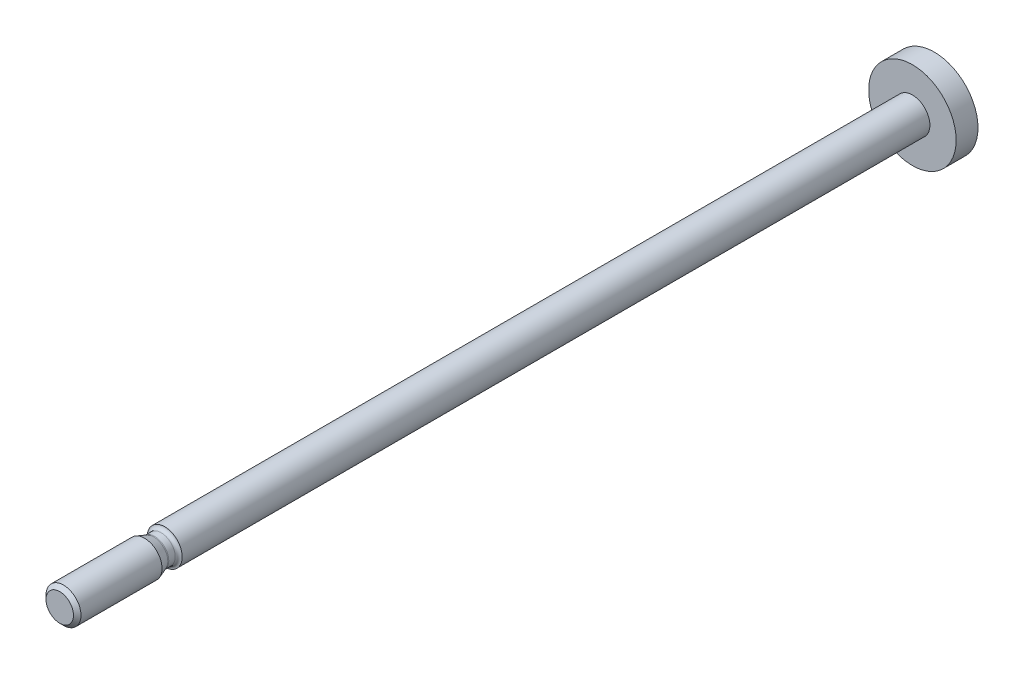
SolidWorks part; units mm, degrees
ref_plane "Front Plane" through (0, 0, 0) normal (0, 0, 1) x (1, 0, 0)
ref_plane "Top Plane" through (0, 0, 0) normal (0, 1, 0) x (1, 0, 0)
ref_plane "Right Plane" through (0, 0, 0) normal (1, 0, 0) x (0, 0, -1)
sketch "Sketch1" plane through (0, 0, 0) normal (1, 0, 0) x (0, 0, -1)
  line L0 (-4, 0) -> (-4, 2)
  line L1 (-4, 2) -> (81.5, 2)
  line L2 (81.5, 2) -> (81.5, 5)
  line L3 (81.5, 5) -> (84, 5)
  line L4 (84, 5) -> (84, 0)
  line L5 (84, 0) -> (-4, 0)
  line L6 (84, 0) -> (-4, 0) construction
revolve "Revolve1" add sketch "Sketch1" angle 360 about L6 reverse direction yes
sketch "Sketch2" plane through (0, 0, 0) normal (1, 0, 0) x (0, 0, -1)
  line L0 (-16, 0) -> (-16, 1.5705)
  line L1 (-16, 1.5705) -> (-15.5705, 2)
  line L2 (-15.5705, 2) -> (-6.299, 2)
  line L3 (-6.299, 2) -> (-5.2663, 1.6241)
  line L4 (-5.1295, 1.6) -> (-4.4, 1.6)
  line L5 (-4, 2) -> (-3, 2)
  line L6 (-3, 2) -> (-3, 0)
  line L7 (-3, 0) -> (-16, 0)
  line L8 (-3, 0) -> (-16, 0) construction
  arc A0 (-5.2663, 1.6241) -> (-5.1295, 1.6) centre (-5.1295, 2) ccw
  arc A1 (-4.4, 1.6) -> (-4, 2) centre (-4.4, 2) ccw
revolve "Revolve2" add sketch "Sketch2" angle 360 about L8 reverse direction yes
cosmetic thread "Cosmetic Thread1" parameters "D1"=9.701, "D2"=3.141
ref_plane "Plane1" through (0, 0, 4) normal (0, 0, 1) x (1, 0, 0)
ref_plane "Plane2" through (0, 0, -174) normal (0, 0, 1) x (1, 0, 0)
ref_plane "Plane3" through (0, 0, 12) normal (0, 0, 1) x (1, 0, 0)
ref_plane "Plane4" through (0, 0, 8.2) normal (0, 0, 1) x (1, 0, 0)
ref_plane "FDT_KSAUFSATZ XY" through (0, 0, 8.2) normal (0, 0, 1) x (1, 0, 0)
ref_plane "FDT_KSAUFSATZ XZ" through (0, 0, 0) normal (0, 1, 0) x (1, 0, 0)
ref_plane "FDT_KSAUFSATZ YZ" through (0, 0, 0) normal (-1, 0, 0) x (0, 0, 1)
ref_axis "FDT_KSAUFSATZ X" through (80.9, 0, 8.2) along (-1, 0, 0)
ref_axis "FDT_KSAUFSATZ Y" through (0, 50, 8.2) along (0, -1, 0)
ref_axis "FDT_KSAUFSATZ Z" through (0, 0, 80.9) along (0, 0, -1)
sketch3d "FDT_KSAUFSATZ"
  point P0 (0, 0, 8.2)
ref_plane "FDT_NUT XY" through (0, 0, 8.2) normal (0, 0, 1) x (1, 0, 0)
ref_plane "FDT_NUT XZ" through (0, 0, 0) normal (0, 1, 0) x (1, 0, 0)
ref_plane "FDT_NUT YZ" through (0, 0, 0) normal (-1, 0, 0) x (0, 0, 1)
ref_axis "FDT_NUT X" through (80.9, 0, 8.2) along (-1, 0, 0)
ref_axis "FDT_NUT Y" through (0, 50, 8.2) along (0, -1, 0)
ref_axis "FDT_NUT Z" through (0, 0, 80.9) along (0, 0, -1)
sketch3d "FDT_NUT"
  point P0 (0, 0, 8.2)
ref_plane "KS XY" through (0, 0, 0) normal (0, 0, -1) x (-1, 0, 0)
ref_plane "KS XZ" through (0, 0, 0) normal (0, 1, 0) x (1, 0, 0)
ref_plane "KS YZ" through (0, 0, 0) normal (1, 0, 0) x (0, 0, -1)
ref_axis "KS X" through (-80.9, 0, 0) along (1, 0, 0)
ref_axis "KS Y" through (0, 50, 0) along (0, -1, 0)
ref_axis "KS Z" through (0, 0, -80.9) along (0, 0, 1)
sketch3d "KS"
  point P0 (0, 0, 0)
ref_plane "NUT1 XY" through (0, 0, 12) normal (0, 0, 1) x (1, 0, 0)
ref_plane "NUT1 XZ" through (0, 0, 0) normal (0, -1, 0) x (-1, 0, 0)
ref_plane "NUT1 YZ" through (0, 0, 0) normal (1, 0, 0) x (0, 0, -1)
ref_axis "NUT1 X" through (-80.9, 0, 12) along (1, 0, 0)
ref_axis "NUT1 Y" through (0, -50, 12) along (0, 1, 0)
ref_axis "NUT1 Z" through (0, 0, 80.9) along (0, 0, -1)
sketch3d "NUT1"
  point P0 (0, 0, 12)
